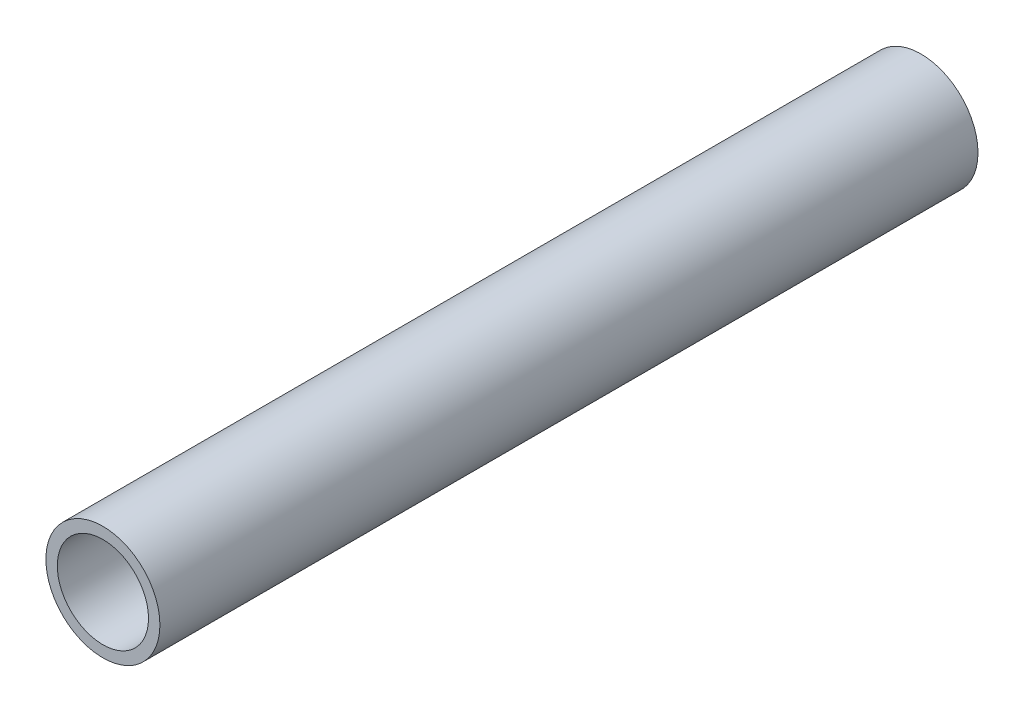
SolidWorks part; units mm, degrees
ref_plane "Front Plane" through (0, 0, 0) normal (0, 0, 1) x (1, 0, 0)
ref_plane "Top Plane" through (0, 0, 0) normal (0, 1, 0) x (1, 0, 0)
ref_plane "Right Plane" through (0, 0, 0) normal (1, 0, 0) x (0, 0, -1)
sketch "Sketch2" plane through (0, 0, 0) normal (0, 0, 1) x (1, 0, 0)
  circle A0 centre (0, 0) radius 10
  circle A1 centre (0, 0) radius 8
extrude "Boss-Extrude1" add sketch "Sketch2" along normal blind 143.5
